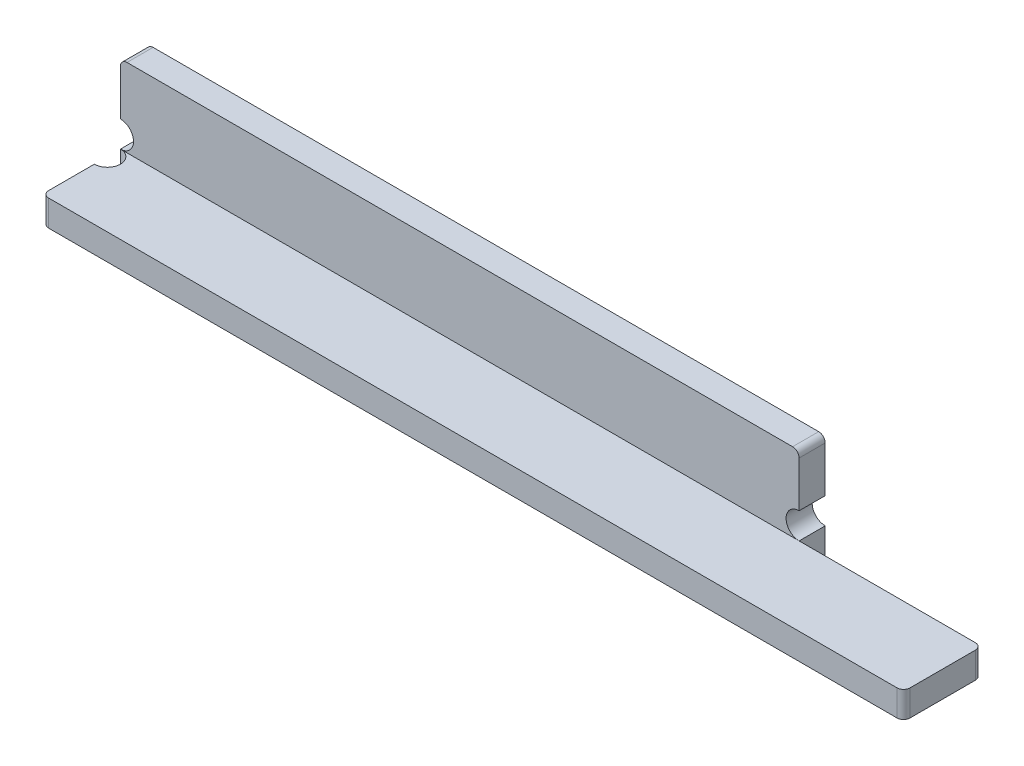
SolidWorks part; units mm, degrees
material "PET"
ref_plane "Front Plane" through (0, 0, 0) normal (0, 0, 1) x (1, 0, 0)
ref_plane "Top Plane" through (0, 0, 0) normal (0, 1, 0) x (1, 0, 0)
ref_plane "Right Plane" through (0, 0, 0) normal (1, 0, 0) x (0, 0, -1)
sketch "Sketch1" plane through (0, 0, 0) normal (0, 1, 0) x (1, 0, 0)
  line L0 (0, 0) -> (0, 17.5)
  line L1 (0, 17.5) -> (86, 17.5)
  line L2 (86, 17.5) -> (86, 2.5)
  line L3 (86, 2.5) -> (130, 2.5)
  line L4 (130, 2.5) -> (130, -2.5)
  line L5 (130, -2.5) -> (165, -2.5)
  line L6 (165, -2.5) -> (165, -17.5)
  line L7 (165, -17.5) -> (0, -17.5)
  line L8 (0, -17.5) -> (0, 0)
  dimension "D1" = 5
  dimension "D2" = 15
  dimension "D3" = 165
  dimension "D4" = 130
  dimension "D5" = 86
extrude "base" add sketch "Sketch1" along normal blind 5
sketch "Sketch2" plane through (0, 5, 0) normal (0, 1, 0) x (1, 0, 0)
  line L0 (0, 17.5) -> (0, -17.5) construction
  line L1 (130, 2.5) -> (0, 2.5)
  line L2 (130, 2.5) -> (130, -2.5)
  line L3 (130, -2.5) -> (0, -2.5)
  line L4 (0, 2.5) -> (0, -2.5)
  line L5 (165, -2.5) -> (130, -2.5) construction
extrude "middle_extrusion" add sketch "Sketch2" along normal blind 15
sketch "Sketch3" plane through (0, 5, 0) normal (0, 1, 0) x (1, 0, 0)
  line L0 (0, -2.5) -> (0, -17.5) construction
  line L1 (0, -7.5) -> (0, -2.5)
  line L2 (0, 2.5) -> (0, 7.5)
  line L3 (0, 17.5) -> (0, 2.5) construction
  line L4 (86, 2.5) -> (86, 7.5)
  line L5 (86, 2.5) -> (86, 17.5) construction
  arc A0 (0, -2.5) -> (0, -7.5) centre (0, -5) cw
  arc A1 (0, 2.5) -> (0, 7.5) centre (0, 5) ccw
  arc A2 (86, 2.5) -> (86, 7.5) centre (86, 5) cw
  point P3 (0, -5)
  dimension "D1" = 5
extrude "fancy_cutout" cut sketch "Sketch3" against normal through all
sketch "Sketch4" plane through (0, 0, 2.5) normal (0, 0, 1) x (1, 0, 0)
  line L0 (0, 5) -> (0, 10)
  line L1 (0, 20) -> (0, 5) construction
  line L2 (130, 5) -> (130, 10)
  line L3 (130, 20) -> (130, 5) construction
  arc A0 (0, 10) -> (0, 5) centre (0, 7.5) cw
  arc A1 (130, 10) -> (130, 5) centre (130, 7.5) ccw
  point P12 (0, 7.5)
  dimension "D1" = 5
extrude "fancy_cutout_middle" cut sketch "Sketch4" against normal through all
fillet "overall_fillets" radius 1.25 7 edges at (0, 2.5, 17.5) (165, 2.5, 17.5) (165, 2.5, 2.5) (130, 20, 0) (0, 20, 0) (86, 2.5, -17.5) (0, 2.5, -17.5)
